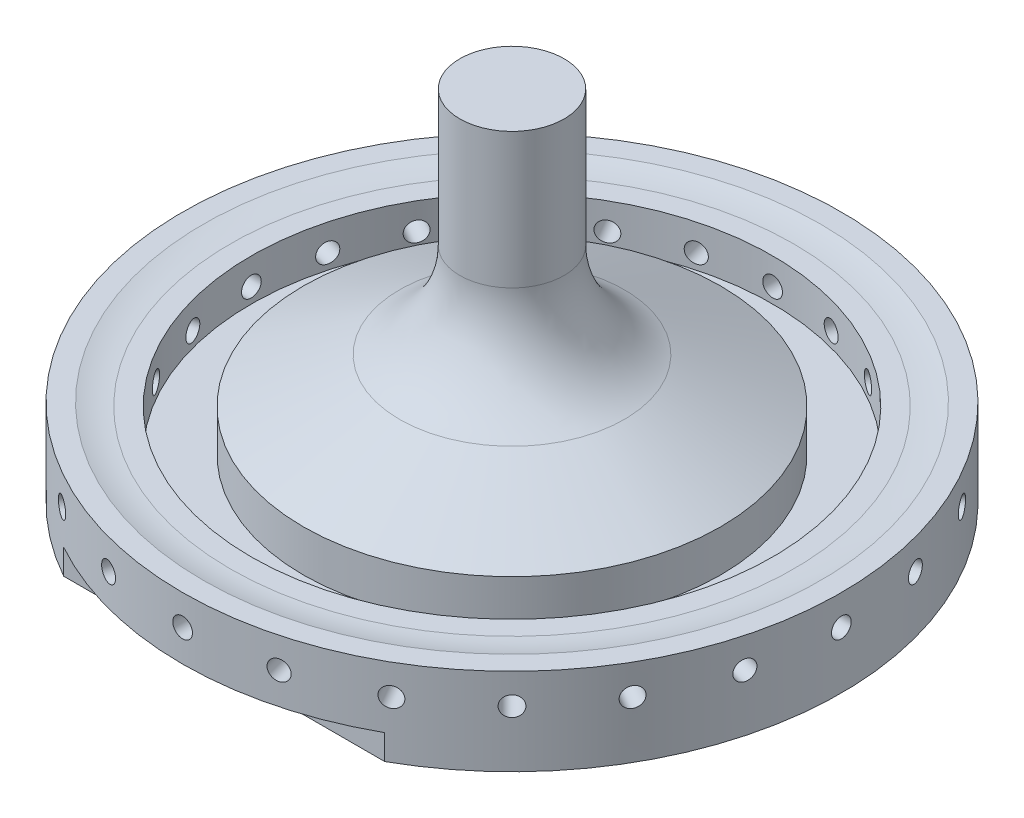
SolidWorks part; units mm, degrees
ref_plane "Front Plane" through (0, 0, 0) normal (0, 0, 1) x (1, 0, 0)
ref_plane "Top Plane" through (0, 0, 0) normal (0, 1, 0) x (1, 0, 0)
ref_plane "Right Plane" through (0, 0, 0) normal (1, 0, 0) x (0, 0, -1)
sketch "Sketch1" plane through (0, 0, 0) normal (0, 0, 1) x (1, 0, 0)
  line L0 (0, 0) -> (0, -33.5996) construction
  line L1 (0, 0) -> (3.175, 0)
  line L2 (3.175, 0) -> (3.175, -8.255)
  line L7 (20.0585, -21.822) -> (0, -21.822)
  line L8 (0, -21.822) -> (0, 0)
  line L9 (18.7885, -16.5256) -> (20.0585, -16.5256)
  line L10 (20.0585, -16.5256) -> (20.0585, -21.822)
  line L12 (18.7885, -16.5256) -> (22.6276, -15.4969) construction
  line L13 (15.875, -16.742) -> (15.875, -19.282)
  line L14 (15.875, -19.282) -> (12.7, -19.282)
  line L15 (12.7, -19.282) -> (12.7, -16.742)
  line L16 (15.875, -16.742) -> (17.145, -16.742)
  line L18 (6.8414, -14.0101) -> (12.7, -16.742)
  arc A0 (17.145, -16.742) -> (18.7885, -16.5256) centre (17.145, -10.392) ccw
  arc A1 (3.175, -8.255) -> (6.8414, -14.0101) centre (9.525, -8.255) ccw
  dimension "D8" = 3.175
  dimension "D2" = 6.35
  dimension "D3" = 6.35
  dimension "D4" = 8.255
  dimension "D5" = 1.27
  dimension "D6" = 15
  dimension "D7" = 65
  dimension "D9" = 1.27
  dimension "D10" = 2.54
  dimension "D12" = 2.54
  dimension "D13" = 25.4
revolve "Revolve1" add sketch "Sketch1" angle 360 about L0
ref_plane "Tangent Plane" through (0, 0, 20.0585) normal (0, 0, 1) x (1, 0, 0)
sketch "Sketch2" plane through (0, 0, 20.0585) normal (0, 0, 1) x (1, 0, 0)
  line L0 (15.875, -19.282) -> (-15.875, -19.282) construction
  line L1 (15.875, -19.282) -> (-15.875, -19.282) construction
  circle A0 centre (0, -18.3645) radius 0.6
  dimension "D1" = 1.2
  dimension "D2" = 0.635
extrude "Hole" cut sketch "Sketch2" against normal up to next
pattern_circular "Hole Pattern" count 24 over 360 about axis through (0, -16.5256, 0) along (0, 1, 0) of "Hole"
sketch "Sketch3" plane through (0, 0, 20.0585) normal (0, 0, 1) x (1, 0, 0)
  line L1 (-12.7, -20.298) -> (12.7, -20.298)
  line L2 (-12.7, -20.298) -> (-12.7, -21.822)
  line L3 (-12.7, -21.822) -> (12.7, -21.822)
  line L4 (12.7, -20.298) -> (12.7, -21.822)
  line L6 (-20.0585, -21.822) -> (20.0585, -21.822) construction
  line L7 (-20.0585, -21.822) -> (20.0585, -21.822) construction
  point P4 (0, -21.822)
  dimension "D1" = 25.4
  dimension "D2" = 1.524
extrude "Flat" cut sketch "Sketch3" against normal blind 2.54
mirror "Flats" about plane through (0, 0, 0) normal (0, 0, 1) of "Flat"
